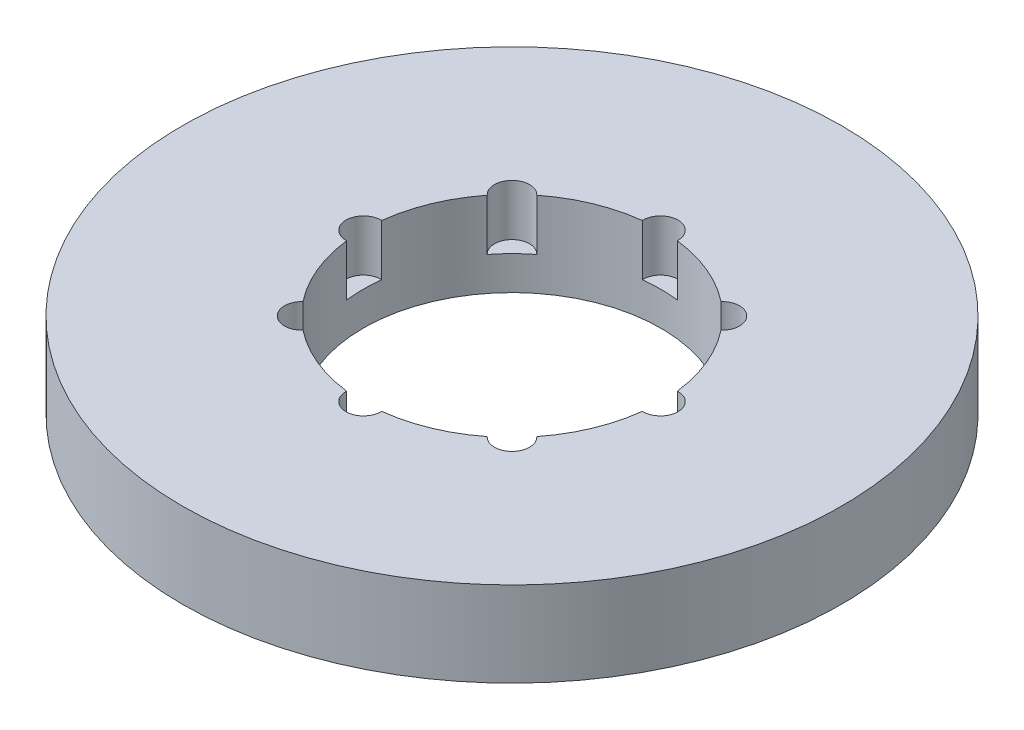
SolidWorks part; units mm, degrees
ref_plane "Front Plane" through (0, 0, 0) normal (0, 0, 1) x (1, 0, 0)
ref_plane "Top Plane" through (0, 0, 0) normal (0, 1, 0) x (1, 0, 0)
ref_plane "Right Plane" through (0, 0, 0) normal (1, 0, 0) x (0, 0, -1)
sketch "Sketch1" plane through (0, 0, 0) normal (0, 1, 0) x (1, 0, 0)
  circle A0 centre (0, 0) radius 77.5
  dimension "FLANGE_OD" = 155
extrude "Boss-Extrude1" add sketch "Sketch1" along normal blind 20
sketch "Sketch2" plane through (0, 0, 0) normal (0, 1, 0) x (1, 0, 0)
  circle A0 centre (0, 0) radius 35
  dimension "BORE_D" = 70
extrude "Cut-Extrude1" cut sketch "Sketch2" along normal through all
sketch "Sketch3" plane through (0, 20, 0) normal (0, 1, 0) x (1, 0, 0)
  circle A0 centre (0, 0) radius 34.9116 construction
  circle A1 centre (-34.9116, 0) radius 4.1246
  dimension "BOLT_D" = 8.2492
  dimension "BOLT_PCD" = 69.8232
extrude "Cut-Extrude2" cut sketch "Sketch3" against normal blind 12.0635
pattern_circular "CirPattern1" count 8 over 360 about axis through (0, 0, 0) along (0, 1, 0) of "Cut-Extrude2"
